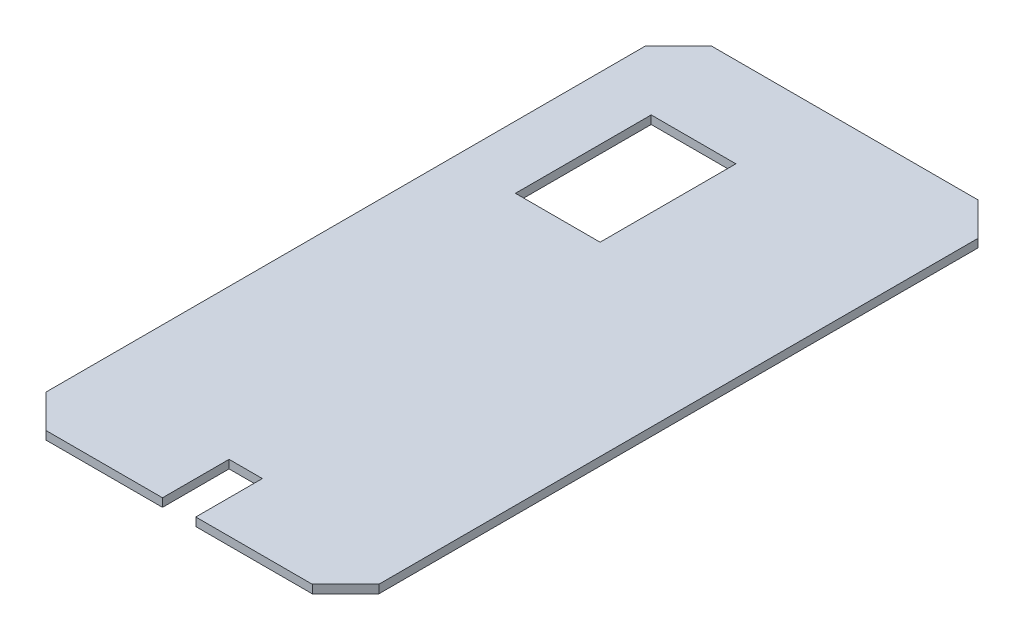
SolidWorks part; units mm, degrees
ref_plane "Front Plane" through (0, 0, 0) normal (0, 0, 1) x (1, 0, 0)
ref_plane "Top Plane" through (0, 0, 0) normal (0, 1, 0) x (1, 0, 0)
ref_plane "Right Plane" through (0, 0, 0) normal (1, 0, 0) x (0, 0, -1)
sketch "Sketch2" plane through (0, 0, 0) normal (0, 1, 0) x (1, 0, 0)
  line L0 (0, 12.7) -> (0, 241.3)
  line L1 (12.7, 254) -> (114.3, 254)
  line L2 (127, 241.3) -> (127, 12.7)
  line L3 (114.3, 0) -> (12.7, 0)
  line L4 (0, 241.3) -> (12.7, 254)
  line L5 (114.3, 254) -> (127, 241.3)
  line L6 (127, 12.7) -> (114.3, 0)
  line L7 (12.7, 0) -> (0, 12.7)
  line L8 (63.5, 254) -> (63.5, -26.6567) construction
  line L10 (0, 127) -> (136.1553, 127) construction
  line L17 (57.15, 25.4) -> (69.85, 25.4)
  line L18 (57.15, 25.4) -> (57.15, 0)
  line L19 (57.15, 0) -> (69.85, 0)
  line L20 (69.85, 25.4) -> (69.85, 0)
  line L21 (57.15, 25.4) -> (69.85, 0) construction
  line L22 (57.15, 0) -> (69.85, 25.4) construction
  line L23 (23.8737, 219.7356) -> (56.184, 219.7356)
  line L24 (23.8737, 219.7356) -> (23.8737, 167.9304)
  line L25 (23.8737, 167.9304) -> (56.184, 167.9304)
  line L26 (56.184, 219.7356) -> (56.184, 167.9304)
  line L27 (23.8737, 219.7356) -> (56.184, 167.9304) construction
  line L28 (23.8737, 167.9304) -> (56.184, 219.7356) construction
  point P0 (63.5, 127)
  point P1 (40.0289, 193.833)
  point P3 (63.5, 12.7)
  point P19 (0, 0)
  point P20 (40.0289, 193.833)
  point P37 (127, 127)
  point P42 (63.5, 0)
  dimension "D14" = 101.6
  dimension "D16" = 12.7
  dimension "D17" = 254
  dimension "D22" = 228.6
  dimension "D36" = 101.6
  dimension "D37" = 228.6
  dimension "D7" = 127
  dimension "D15" = 12.7
  dimension "D4" = 25.4
  dimension "D5" = 12.7
extrude "Boss-Extrude1" add sketch "Sketch2" along normal blind 3.175 contours L7 L3 L6 L2 L5 L1 L4 L0 region at (64.8122, 0, -124.495)
